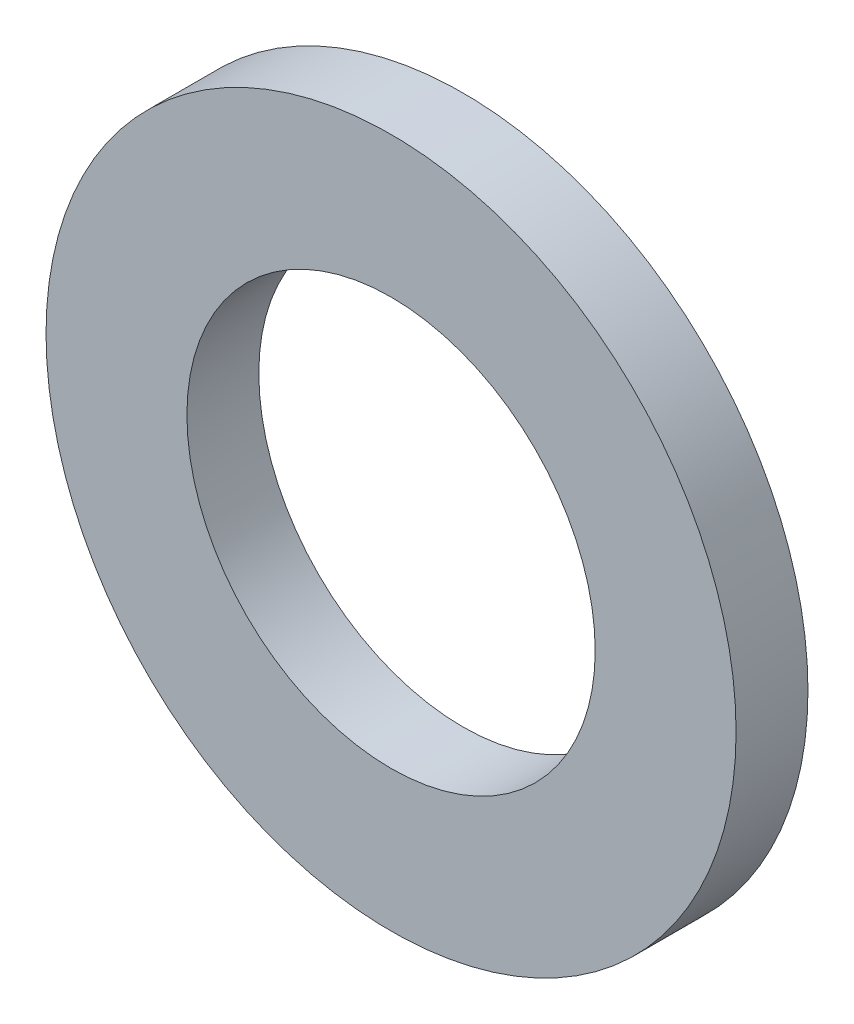
SolidWorks part; units mm, degrees
ref_plane "Front Plane" through (0, 0, 0) normal (0, 0, 1) x (1, 0, 0)
ref_plane "Top Plane" through (0, 0, 0) normal (0, 1, 0) x (1, 0, 0)
ref_plane "Right Plane" through (0, 0, 0) normal (1, 0, 0) x (0, 0, -1)
sketch "Sketch1" plane through (0, 0, 0) normal (0, 0, 1) x (1, 0, 0)
  circle A0 centre (0, 0) radius 7.1
  circle A1 centre (0, 0) radius 12
extrude "Boss-Extrude1" add sketch "Sketch1" along normal blind 2.5
